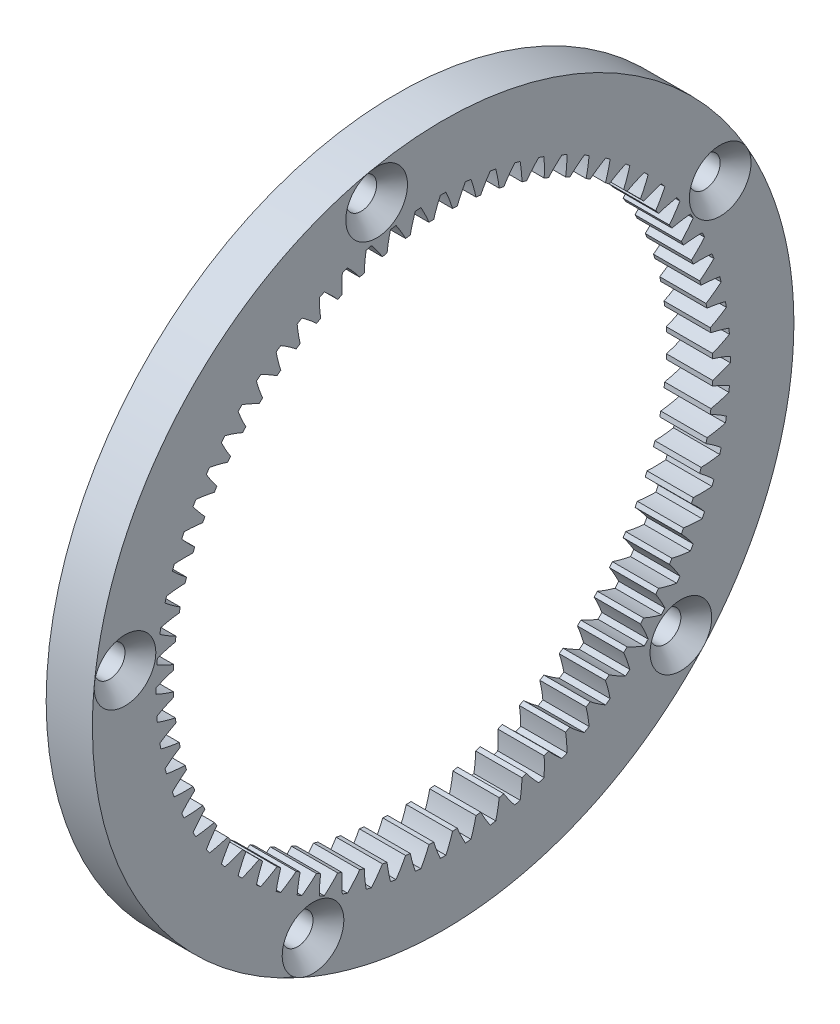
SolidWorks part; units mm, degrees
ref_plane "Plane1" through (0, 0, 0) normal (0, 0, 1) x (1, 0, 0)
ref_plane "Plane2" through (0, 0, 0) normal (0, 1, 0) x (1, 0, 0)
ref_plane "Plane3" through (0, 0, 0) normal (1, 0, 0) x (0, 0, -1)
sketch "HoldingSke" plane through (0, 0, 0) normal (0, 1, 0) x (1, 0, 0)
  line L0 (0, 0) -> (0.618, -1.9021)
  line L1 (-15, 0) -> (100, 0) construction
  line L2 (0, 0) -> (-2.1039, 2.3779)
  line L3 (0, 0) -> (-11.863, 4.5341)
  line L4 (0, 0) -> (2.6687, 8.2133)
  line L5 (0, 0) -> (-23.7986, -8.8762)
  line L6 (0, 0) -> (-10.5278, -7.1032)
  line L7 (-2.1039, 2.3779) -> (3.3635, 27.1825)
  line L8 (-76.2, 2.8779) -> (-54.61, 2.8779)
  line L9 (-71.009, 38.7566) -> (-53.1078, 45.2721)
  line L10 (-76.2, 71.12) -> (104.1128, 71.12)
  line L11 (0, 0) -> (-3, 0)
  line L12 (-76.2, 101.6) -> (-76.181, 101.6)
  line L13 (24.9733, 27.94) -> (52.9518, 28.4284)
  line L14 (24.9733, 27.94) -> (24.9743, 27.94)
  line L15 (24.9733, 27.94) -> (100.4006, 29.5858)
  circle A0 centre (0, 0) radius 22.75
  circle A1 centre (0, 0) radius 12.7
  circle A2 centre (0, 0) radius 12.7
  dimension "MHD" = 25.4
  dimension "Hub_dia" = 25.4
  dimension "Diameter" = 45.5
  dimension "Num_teeth" = 72
  dimension "Pitch_radius" = 180.3128
  dimension "Pitch" = 2
  dimension "Width" = 3
  dimension "Overall_len" = 25.4
  dimension "Show_teeth" = 72
  dimension "Thickness" = 12.7
  dimension "OAL" = 25.4001
  dimension "T_dim" = 21.59
  dimension "Ap" = 20
  dimension "H" = 19.05
  dimension "Backlash" = 0.019
  dimension "Addendum_fac" = 1
  dimension "Dedendum_fac" = 1.25
  dimension "Clearance_fac" = 0.25
  dimension "Dedendum_add" = 0.001
  dimension "Module" = 0.5
sketch "BasProSke" plane through (0, 0, 0) normal (0, 1, 0) x (1, 0, 0)
  line L0 (-10, 0) -> (60, 0) construction
  line L1 (0, 17.5) -> (0, 22.75)
  line L2 (0, 17.5) -> (3, 17.5)
  line L3 (3, 17.5) -> (3, 22.75)
  line L4 (3, 22.75) -> (0, 22.75)
  dimension "Diameter" = 45.5
  dimension "Thickness" = 3
  dimension "Inside_diameter" = 35
revolve "Base-Revolve" add sketch "BasProSke" angle 360 about L0
sketch "TooCutSke" plane through (0, 0, 0) normal (1, 0, 0) x (0, 0, -1)
  line L3 (0.4402, 17.9946) -> (0.4402, 53.6633) construction
  line L4 (0, 0) -> (0, 59.563) construction
  line L5 (0, 0) -> (-2.9804, 68.2625) construction
  line L6 (-8.0066, 14.8879) -> (37.1428, 16.8592) construction
  circle A0 centre (0, 0) radius 18 construction
  circle A1 centre (0, 0) radius 18.626 construction
  circle A2 centre (0, 0) radius 15.223 construction
  circle A3 centre (0, 0) radius 17.4746 construction
  arc A4 (0.6169, 17.4637) -> (0.1808, 18.6251) centre (-8.0066, 14.8879) ccw
  arc A5 (0.6169, 17.4637) -> (-0.6169, 17.4637) centre (0, 0) ccw
  arc A6 (0.1808, 18.6251) -> (-0.1808, 18.6251) centre (0, 0) ccw
  arc A7 (-0.1808, 18.6251) -> (-0.6169, 17.4637) centre (8.0066, 14.8879) ccw
  dimension "Pitch_dia" = 36
  dimension "Base_dia" = 30.446
  dimension "Root_dia" = 37.252
  dimension "Overcut_dia" = 34.9492
  dimension "Flank_rad" = 9
  dimension "Half_ang" = 2.5
  dimension "Half_CT" = 0.4402
extrude "ToothCut" cut sketch "TooCutSke" along normal through all
fillet "Breaks" [suppressed] radius 0.05
fillet "RootFillets" [suppressed] radius 0.126
pattern_circular "TeethCuts" count 72 over 360 about axis through (-10, 0, 0) along (1, 0, 0) of "RootFillets", "Breaks", "ToothCut"
sketch "Sketch1" plane through (3, 0, 0) normal (1, 0, 0) x (0, 0, -1)
  line L0 (-4.3142, 20.2966) -> (0, 0) construction
  line L1 (0, 0) -> (-22.75, 0) construction
  circle A0 centre (-4.3142, 20.2966) radius 1
  circle A1 centre (0, 0) radius 22.75 construction
  dimension "D2" = 2
  dimension "D1" = 78
  dimension "D3" = 20.75
extrude "Cut-Extrude1" cut sketch "Sketch1" against normal up to next
chamfer "Chamfer1" distance 1 angle 45 1 edges at (3, 20.2966, 3.3142)
pattern_circular "CirPattern1" count 5 over 360 about axis through (3, 0, 0) along (-1, 0, 0) of "Cut-Extrude1", "Chamfer1"
equation "' \"Module@HoldingSke\" = 6.35"
equation "' \"Num_teeth@HoldingSke\" = 24"
equation "' \"Ap@HoldingSke\" =  14.5"
equation "' \"Width@HoldingSke\" = 12"
equation "' \"Diameter@HoldingSke\" = 8 * 25.4"
equation "' \"Show_teeth@HoldingSke\" = 100"
equation "' \"Backlash@HoldingSke\" = 0.009 * 25.4"
equation "' \"Addendum_fac@HoldingSke\" = 1.0"
equation "' \"Dedendum_fac@HoldingSke\" = 1.25"
equation "' \"Dedendum_add@HoldingSke\" = 0.00005 * 25.4"
equation "' \"Clearance_fac@HoldingSke\" = 0.25"
equation "\"Pitch@HoldingSke\" = 1 / \"Module@HoldingSke\" "
equation "\"Overcut_dia@TooCutSke\" = (\"Num_teeth@HoldingSke\" - 2 * \"Addendum_fac@HoldingSke\") / \"Pitch@HoldingSke\" - 0.002 * 25.4"
equation "\"Pitch_dia@TooCutSke\" = \"Num_teeth@HoldingSke\" / \"Pitch@HoldingSke\""
equation "\"Base_dia@TooCutSke\" = \"Num_teeth@HoldingSke\" / \"Pitch@HoldingSke\" * cos((\"Ap@HoldingSke\"  * 3.14159265 / 180)) * 0.90"
equation "\"Root_dia@TooCutSke\" = \"Num_teeth@HoldingSke\"  / \"Pitch@HoldingSke\" + 2 *  \"Dedendum_fac@HoldingSke\"/ \"Pitch@HoldingSke\" + \"Dedendum_add@HoldingSke\" * 2"
equation "\"Half_ang@TooCutSke\" = 180 / \"Num_teeth@HoldingSke\""
equation "\"Half_CT@TooCutSke\" = \"Num_teeth@HoldingSke\" / \"Pitch@HoldingSke\" * sin((3.14159265 / 2 / \"Num_teeth@HoldingSke\")) / 2 + 10 * \"Backlash@HoldingSke\" / 4"
equation "\"Flank_rad@TooCutSke\" = \"Num_teeth@HoldingSke\" / \"Pitch@HoldingSke\" / 4"
equation "\"Radius@RootFillets\"= \"Clearance_fac@HoldingSke\" / \"Pitch@HoldingSke\" + \"Dedendum_add@HoldingSke\""
equation "\"Break_rad@Breaks\" = 0.02 / \"Pitch@HoldingSke\" * 5"
equation "\"Num_teeth@TeethCuts\" = int( \"Show_teeth@HoldingSke\" ) + 1"
equation "\"Num_teeth@TeethCuts\" = ((sgn( \"Num_teeth@TeethCuts\" - \"Num_teeth@HoldingSke\" )-1)*( \"Num_teeth@TeethCuts\" - \"Num_teeth@HoldingSke\" ))/-2+ \"Num_teeth@HoldingSke\""
equation "\"Num_teeth@TeethCuts\" = ((sgn( \"Num_teeth@TeethCuts\" - 2.0)+1)*( \"Num_teeth@TeethCuts\" - 2.0))/2 +2.0"
equation "\"Angle@TeethCuts\" = 360.0 / \"Num_teeth@HoldingSke\""
equation "\"Diameter@BasProSke\" = \"Num_teeth@HoldingSke\"  / \"Pitch@HoldingSke\" + 2 *  \"Dedendum_fac@HoldingSke\"/ \"Pitch@HoldingSke\" + \"Dedendum_add@HoldingSke\" * 2 + 0.002 * 25.4"
equation "\"Diameter@BasProSke\" = ((sgn( \"Diameter@BasProSke\"  - \"Diameter@HoldingSke\" )+1)*( \"Diameter@BasProSke\"  - \"Diameter@HoldingSke\" ))/2 + \"Diameter@HoldingSke\""
equation "\"Inside_diameter@BasProSke\" =  (\"Num_teeth@HoldingSke\" - 2 * \"Addendum_fac@HoldingSke\") / \"Pitch@HoldingSke\" "
equation "\"Thickness@BasProSke\"  = \"Width@HoldingSke\""
